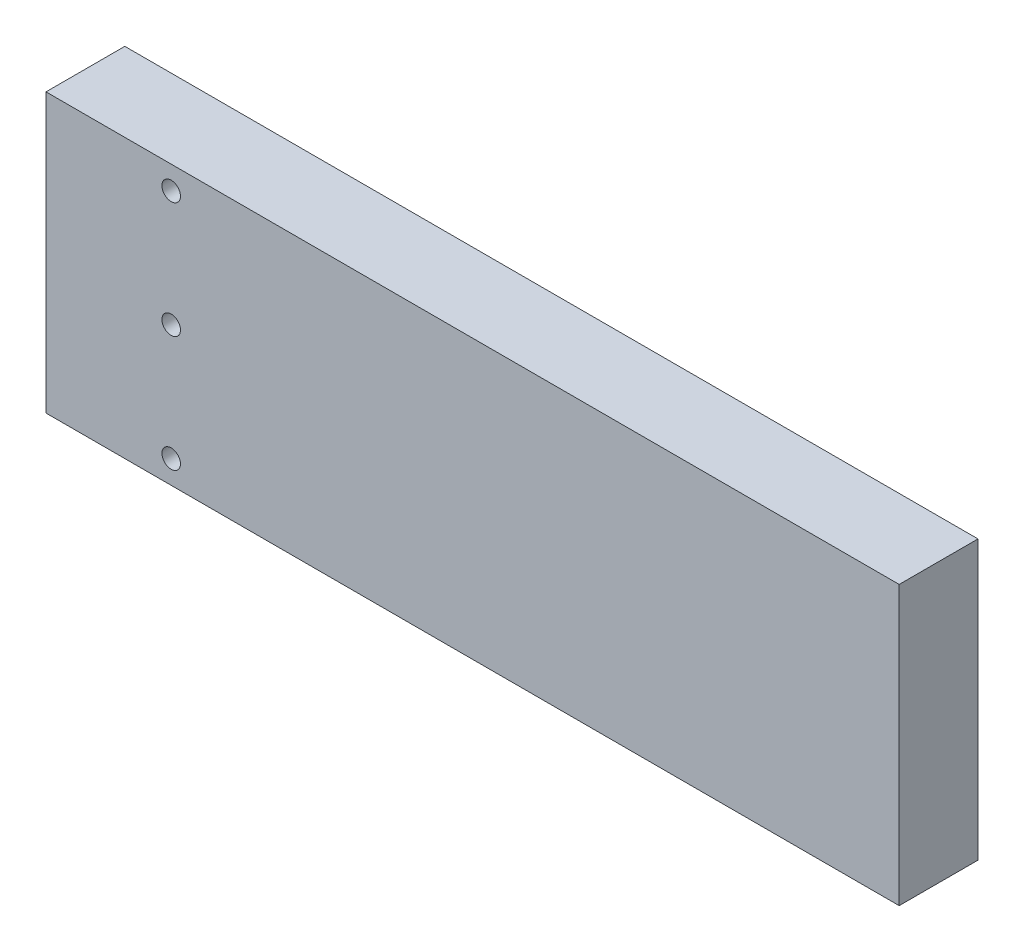
SolidWorks part; units mm, degrees
ref_plane "Plan de face" through (0, 0, 0) normal (0, 0, 1) x (1, 0, 0)
ref_plane "Plan de dessus" through (0, 0, 0) normal (0, 1, 0) x (1, 0, 0)
ref_plane "Plan de droite" through (0, 0, 0) normal (1, 0, 0) x (0, 0, -1)
sketch "Esquisse1" plane through (0, 0, 0) normal (0, 0, 1) x (1, 0, 0)
  line L1 (0, 0) -> (54, 0)
  line L2 (0, 0) -> (0, -60)
  line L3 (0, -60) -> (54, -60)
  line L4 (54, 0) -> (54, -60)
  line L5 (54, 0) -> (130, 0)
  line L6 (54, 0) -> (54, -60)
  line L7 (54, -60) -> (130, -60)
  line L8 (130, 0) -> (130, -60)
  line L9 (130, -60) -> (184, -60)
  line L10 (130, -60) -> (130, 0)
  line L11 (130, 0) -> (184, 0)
  line L12 (184, -60) -> (184, 0)
  circle A0 centre (27, -55) radius 2
  circle A1 centre (27, -30) radius 2
  circle A2 centre (27, -5) radius 2
  point P11 (27, 0)
  dimension "D1" = 4
  dimension "D2" = 4
  dimension "D3" = 4
  dimension "D4" = 60
  dimension "D5" = 54
  dimension "D6" = 0
  dimension "D7" = 0
  dimension "D8" = 0
  dimension "D9" = 30
  dimension "D10" = 5
  dimension "D11" = 5
  dimension "D12" = 54
  dimension "D13" = 130
extrude "Boss.-Extru.1" add sketch "Esquisse1" along normal blind 17 contours L4 L1 L2 L3 A2 A1 A0 | L8 L5 L4 L7 | L9 L12 L11 L8 region at (27, -0.8072, 0) region at (92, -30, 0) region at (157, -30, 0)
